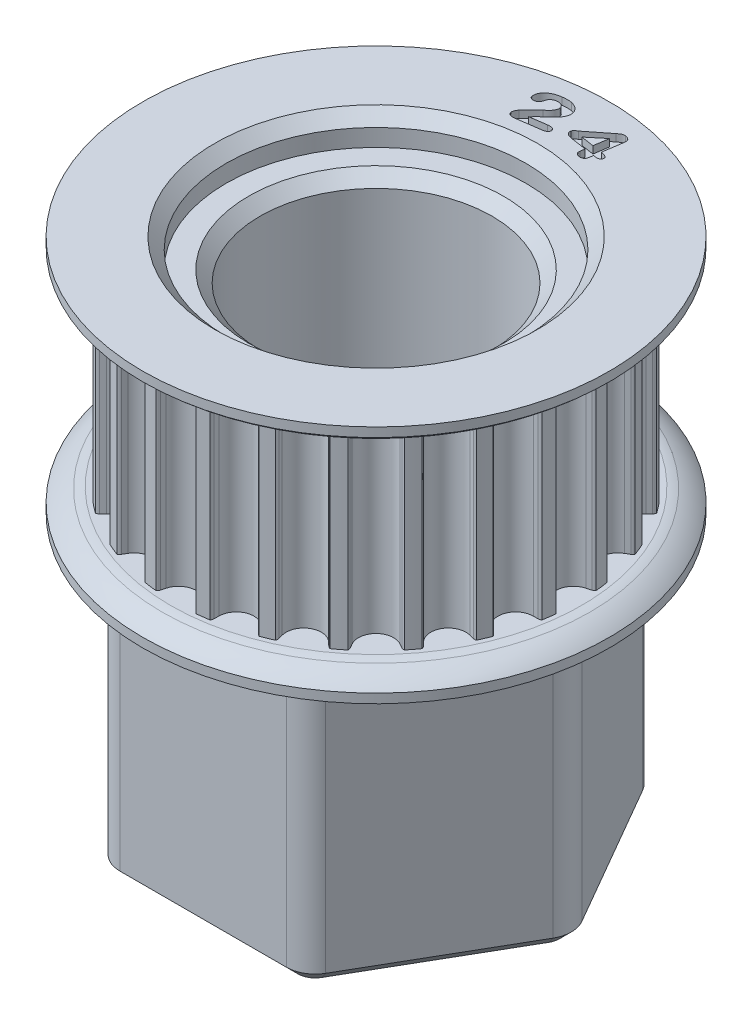
SolidWorks part; units mm, degrees
other "DetailItem2"
material "Markforged"
ref_plane "Front Plane" through (0, 0, 0) normal (0, 0, 1) x (1, 0, 0)
ref_plane "Top Plane" through (0, 0, 0) normal (0, 1, 0) x (1, 0, 0)
ref_plane "Right Plane" through (0, 0, 0) normal (1, 0, 0) x (0, 0, -1)
ref_axis "Centerline" through (0, 8.7312, 0) along (0, -1, 0)
sketch "Sketch1" plane through (0, 0, 0) normal (0, 1, 0) x (1, 0, 0)
  circle A0 centre (0, 0) radius 11.0782
  dimension "OuterDiameter" = 22.1563
extrude "ToothOD" add sketch "Sketch1" along normal mid plane 10.668
sketch "Sketch2" plane through (0, 0, 0) normal (0, 1, 0) x (1, 0, 0)
  line L0 (0, 9.9098) -> (50000, 9.9098) construction
  line L1 (0, 11.0782) -> (50000, 11.0782) construction
  line L2 (0, 0) -> (0, 50000) construction
  arc A0 (-0.937, 10.6282) -> (0, 9.9098) centre (0, 10.88) ccw
  arc A1 (-1.1005, 11.0234) -> (1.1005, 11.0234) centre (0, 0) cw
  circle A2 centre (0, 0) radius 11.0782 construction
  arc A3 (-0.937, 10.6282) -> (-1.0078, 10.88) centre (-11.9754, 7.6618) ccw
  arc A4 (-1.0078, 10.88) -> (-1.1005, 11.0234) centre (-1.2954, 10.7956) ccw
  circle A5 centre (0, 0) radius 11.0782 construction
  arc A6 (0.937, 10.6282) -> (1.0078, 10.88) centre (11.9754, 7.6618) cw
  arc A7 (1.0078, 10.88) -> (1.1005, 11.0234) centre (1.2954, 10.7956) cw
  arc A8 (0, 9.9098) -> (0.937, 10.6282) centre (0, 10.88) ccw
  dimension "D1" = 1.9406
  dimension "D3" = 22.86
  dimension "D4" = 0.5994
  dimension "D2" = 1.1684
  dimension "D5" = 1.2954
extrude "ToothProfile" cut sketch "Sketch2" against normal through all both and the other way through all
pattern_circular "ToothPattern" count 24 over 360 about axis through (0, 5.334, 0) along (0, -1, 0) of "ToothProfile"
sketch "Sketch4" plane through (0, 0, 0) normal (0, 0, 1) x (1, 0, 0)
  line L0 (0, -5.334) -> (11.3322, -5.334)
  line L1 (0, -6.604) -> (12.8562, -6.604)
  line L2 (0, -6.604) -> (0, -5.334)
  line L3 (12.8562, -6.604) -> (12.8562, -6.096)
  line L4 (0, 0) -> (50000, 0) construction
  line L5 (12.8562, 6.604) -> (12.8562, 6.096)
  line L6 (0, 6.604) -> (0, 5.334)
  line L7 (0, 6.604) -> (12.8562, 6.604)
  line L8 (0, 5.334) -> (11.3322, 5.334)
  arc A0 (11.3322, -5.334) -> (11.7872, -5.4266) centre (11.0525, -7.872) cw
  arc A2 (11.7872, -5.4266) -> (12.8562, -6.096) centre (10.6547, -8.4234) cw
  arc A3 (11.7872, 5.4266) -> (12.8562, 6.096) centre (10.6547, 8.4234) ccw
  arc A4 (11.3322, 5.334) -> (11.7872, 5.4266) centre (11.0525, 7.872) ccw
  dimension "D5" = 2.5534
  dimension "D6" = 3.2036
  dimension "FlangeID" = 11.3322
  dimension "FlangeOD" = 12.8562
  dimension "D2" = 0.508
  dimension "D3" = 5.334
  dimension "D4" = 13.208
  dimension "D7" = 0.762
  dimension "D8" = 0.6694
  dimension "D10" = 1.0689
revolve "Flange" add sketch "Sketch4" angle 360 about axis through (0, 8.7312, 0) along (0, -1, 0)
sketch "Sketch6" plane through (0, 0, 0) normal (0, 0, 1) x (1, 0, 0)
  line L0 (0, -6.604) -> (0, -7.9375) construction
  line L1 (-12.8562, -6.604) -> (12.8562, -6.604) construction
  line L2 (0, -7.9375) -> (8.2931, -7.9375) construction
  line L3 (8.2931, -7.9375) -> (8.2931, -6.604) construction
  line L4 (8.2931, -6.604) -> (0, -6.604) construction
  line L5 (0, 0) -> (50000, 0) construction
  line L6 (8.2931, 6.604) -> (0, 6.604)
  line L7 (8.2931, 7.9375) -> (8.2931, 6.604)
  line L8 (0, 7.9375) -> (8.2931, 7.9375)
  line L9 (0, 6.604) -> (0, 7.9375)
  line L11 (36.0254, 12.0878) -> (29.4657, 15.4613) construction
  line L12 (29.4657, 15.4613) -> (23.2643, 11.4672) construction
  line L13 (23.2643, 11.4672) -> (23.6226, 4.0996) construction
  line L14 (23.6226, 4.0996) -> (30.1823, 0.7261) construction
  line L15 (30.1823, 0.7261) -> (36.3837, 4.7202) construction
  line L16 (36.3837, 4.7202) -> (36.0254, 12.0878) construction
  circle A0 centre (29.824, 8.0937) radius 6.3881 construction
  circle A1 centre (29.824, 8.0937) radius 8.2931 construction
  dimension "D2" = 12.7762
  dimension "D1" = 15.875
  dimension "D4" = 8.2931
  dimension "D3" = 1.905
  dimension "D5" = 1.3335
revolve "TopBearingBoss" [suppressed] add sketch "Sketch6" angle 360 about axis through (0, 8.7312, 0) along (0, -1, 0)
mirror "BottomBearingBoss" [suppressed] about plane through (0, 0, 0) normal (0, 1, 0)
sketch "Sketch7" plane through (0, 0, 0) normal (0, -1, 0) x (1, 0, 0)
  line L1 (3.6882, 6.3881) -> (-3.6882, 6.3881) construction
  line L2 (-3.6882, 6.3881) -> (-7.3763, 0) construction
  line L3 (-7.3763, 0) -> (-3.6882, -6.3881) construction
  line L4 (-3.6882, -6.3881) -> (3.6882, -6.3881) construction
  line L5 (3.6882, -6.3881) -> (7.3763, 0) construction
  line L6 (7.3763, 0) -> (3.6882, 6.3881) construction
  circle A0 centre (0, 0) radius 6.3881
  dimension "HexBoreDi," = 12.7762
extrude "Bore" cut sketch "Sketch7" against normal through all both and the other way through all
sketch "Sketch9" plane through (0, 6.604, 0) normal (0, 1, 0) x (1, 0, 0)
  arc A0 (-6.4927, -6.4927) -> (6.4927, -6.4927) centre (0, 0) cw construction
  text T0 "24" font "Arial Rounded MT Bold" height 4.572
  point P3 (0, 9.1821)
  dimension "D1" = 9.1821
  dimension "D2" = 270
extrude "Large Tooth Count" [suppressed] cut sketch "Sketch9" against normal blind 0.4 and the other way through all
sketch "Sketch11" plane through (0, 6.604, 0) normal (0, 1, 0) x (1, 0, 0)
  arc A0 (-6.8456, -6.8456) -> (6.8456, -6.8456) centre (0, 0) cw construction
  circle A1 centre (0, 0) radius 12.8562 construction
  text T0 "<b>24</b>" font "Arial Rounded MT Bold" height 2.286
  point P6 (0, 9.6812)
  dimension "D1" = 3.175
  dimension "D3" = 270
extrude "Small Tooth Count" cut sketch "Sketch11" against normal blind 0.4 and the other way through all
sketch "Sketch12" plane through (0, -6.604, 0) normal (0, -1, 0) x (1, 0, 0)
  line L1 (5.4993, -9.525) -> (10.9985, 0)
  line L2 (10.9985, 0) -> (5.4993, 9.525)
  line L3 (5.4993, 9.525) -> (-5.4993, 9.525)
  line L4 (-5.4993, 9.525) -> (-10.9985, 0)
  line L5 (-10.9985, 0) -> (-5.4993, -9.525)
  line L6 (-5.4993, -9.525) -> (5.4993, -9.525)
  circle A0 centre (0, 0) radius 6.3881 construction
  circle A1 centre (0, 0) radius 6.3881
  circle A2 centre (0, 0) radius 9.525 construction
  dimension "D1" = 19.05
extrude "Boss-Extrude1" add sketch "Sketch12" along normal blind 15.24
sketch "Sketch27" plane through (0, 6.604, 0) normal (0, 1, 0) x (1, 0, 0)
  circle A0 centre (0, 0) radius 8.255
  dimension "D1" = 16.51
extrude "Cut-Extrude1" cut sketch "Sketch27" against normal blind 1.5875
fillet "Fillet1" radius 1.5875 6 edges at (-5.4993, -14.224, 9.525) (5.4993, -14.224, 9.525) (10.9985, -14.224, 0) (5.4993, -14.224, -9.525) (-10.9985, -14.224, 0) (-5.4993, -14.224, -9.525)
sketch "Sketch25" plane through (0, -6.604, 0) normal (0, -1, 0) x (1, 0, 0)
  line L6 (-4.5827, -9.525) -> (4.5827, -9.525)
  line L7 (-10.5403, -0.7937) -> (-5.9575, -8.7313)
  line L8 (-5.9575, 8.7312) -> (-10.5403, 0.7938)
  line L9 (4.5827, 9.525) -> (-4.5827, 9.525)
  line L10 (10.5403, 0.7938) -> (5.9575, 8.7312)
  line L11 (5.9575, -8.7312) -> (10.5403, -0.7937)
  line L12 (-4.5827, -9.525) -> (4.5827, -9.525)
  line L13 (-10.5403, -0.7937) -> (-5.9575, -8.7313)
  line L14 (-5.9575, 8.7312) -> (-10.5403, 0.7938)
  line L15 (4.5827, 9.525) -> (-4.5827, 9.525)
  line L16 (10.5403, 0.7938) -> (5.9575, 8.7312)
  line L17 (5.9575, -8.7312) -> (10.5403, -0.7937)
  arc A6 (-5.9575, -8.7313) -> (-4.5827, -9.525) centre (-4.5827, -7.9375) ccw
  arc A7 (-10.5403, 0.7938) -> (-10.5403, -0.7937) centre (-9.1654, 0) ccw
  arc A8 (-4.5827, 9.525) -> (-5.9575, 8.7312) centre (-4.5827, 7.9375) ccw
  arc A9 (5.9575, 8.7312) -> (4.5827, 9.525) centre (4.5827, 7.9375) ccw
  arc A10 (10.5403, -0.7937) -> (10.5403, 0.7938) centre (9.1654, 0) ccw
  arc A11 (4.5827, -9.525) -> (5.9575, -8.7312) centre (4.5827, -7.9375) ccw
  arc A12 (-5.9575, -8.7313) -> (-4.5827, -9.525) centre (-4.5827, -7.9375) ccw
  arc A13 (-10.5403, 0.7938) -> (-10.5403, -0.7937) centre (-9.1654, 0) ccw
  arc A14 (-4.5827, 9.525) -> (-5.9575, 8.7312) centre (-4.5827, 7.9375) ccw
  arc A15 (5.9575, 8.7312) -> (4.5827, 9.525) centre (4.5827, 7.9375) ccw
  arc A16 (10.5403, -0.7937) -> (10.5403, 0.7938) centre (9.1654, 0) ccw
  arc A17 (4.5827, -9.525) -> (5.9575, -8.7312) centre (4.5827, -7.9375) ccw
  dimension "D1" = 0
sweep "Cut-Sweep1" cut path "Sketch25" circular profile diameter 0.635 parameters "D3"=0.635
fillet "Fillet2" radius 1.27 24 edges at (-5.5352, -6.604, 9.5873) (0, -6.604, 9.8425) (5.5352, -6.604, 9.5873) (8.5239, -6.604, 4.9213) (11.0704, -6.604, 0) (8.5239, -6.604, -4.9212) (5.5352, -6.604, -9.5873) (0, -6.604, -9.8425) (-5.5352, -6.604, -9.5873) (-8.5239, -6.604, -4.9213) (-11.0704, -6.604, 0) (-10.7529, -6.9215, 0) (-8.2489, -6.9215, -4.7625) (-5.3765, -6.9215, -9.3123) (0, -6.9215, -9.525) (5.3765, -6.9215, -9.3123) (8.2489, -6.9215, -4.7625) (10.7529, -6.9215, 0) (8.2489, -6.9215, 4.7625) (5.3765, -6.9215, 9.3123) (0, -6.9215, 9.525) (-5.3765, -6.9215, 9.3123) (-8.5239, -6.604, 4.9212) (-8.2489, -6.9215, 4.7625)
chamfer "Chamfer1" distance 0.635 angle 45 3 edges at (0, -21.844, -6.3881) (0, 6.604, 8.255) (0, 5.0165, 6.3881)
chamfer "Chamfer2" distance 0.635 angle 45 12 edges at (0, -21.844, -9.525) (5.3765, -21.844, -9.3123) (-5.3765, -21.844, -9.3123) (8.2489, -21.844, -4.7625) (-8.2489, -21.844, -4.7625) (10.7529, -21.844, 0) (-10.7529, -21.844, 0) (8.2489, -21.844, 4.7625) (-8.2489, -21.844, 4.7625) (5.3765, -21.844, 9.3123) (-5.3765, -21.844, 9.3123) (0, -21.844, 9.525)
equation "\"OuterDiameter@Sketch1\"= \"OD\""
equation "\"Teeth\"= \"No_Teeth\""
equation "\"PD\"= \"No_Teeth\" * 3mm / pi"
equation "\"OD\"= \"PD\" - .030"
equation "\"ToothCount@ToothPattern\" = \"Teeth\""
equation "\"Angle\"= 360 / \"Teeth\""
equation "\"AngleSpacing@ToothPattern\" = \"Angle\""
equation "\"FlangeID@Sketch4\"=\"OD\"/2+.01"
equation "\"FlangeOD@Sketch4\"=\"PD\"/2+.055"
equation "\"D3@Sketch4\"=\"Tooth_Face_Length\"/2"
equation "\"Bearing_Feature\"= \"Bearing_Boss\""
equation "\"TopBearingBoss\" = IIF ( \"Bearing_Feature\" > 0 , \"unsuppressed\" , \"suppressed\" )"
equation "\"HexBore\"= \"Hex_Bore\" + \"Print_Tolerance\""
equation "\"HexBoreDi,@Sketch7\"= \"HexBore\""
equation "\"D2@Sketch6\"=\"HexBore\""
equation "\"D4@Sketch6\"=\"HexBore\"/2+.075"
equation "\"Large Tooth Count\" = iif ( \"No_Teeth\" < \"TextTooth\" , \"suppressed\" , \"unsuppressed\" )"
equation "\"Small Tooth Count\"= iif ( \"No_Teeth\" < \"TextTooth\" , \"unsuppressed\" , \"suppressed\" )"
equation "\"BottomBearingBoss\" = iif ( \"Bearing_Feature\" > 1 , \"unsuppressed\" , \"suppressed\" )"
equation "\"ToothFaceLength@ToothOD\" = \"Tooth_Face_Length\""
equation "\"D4@Sketch4\" = \"Width_No_BearingBoss\""
equation "\"D1@Sketch9\"=\"HexBore\"/2+.11"
equation "\"TextTooth\"= iif ( \"Hex_Bore\" <= .380 , 23 , iif ( \"Hex_Bore\" <= .505 , 25 , 16 ) )"
equation "\"D1@Sketch6\"=\"Overall_Width\""
